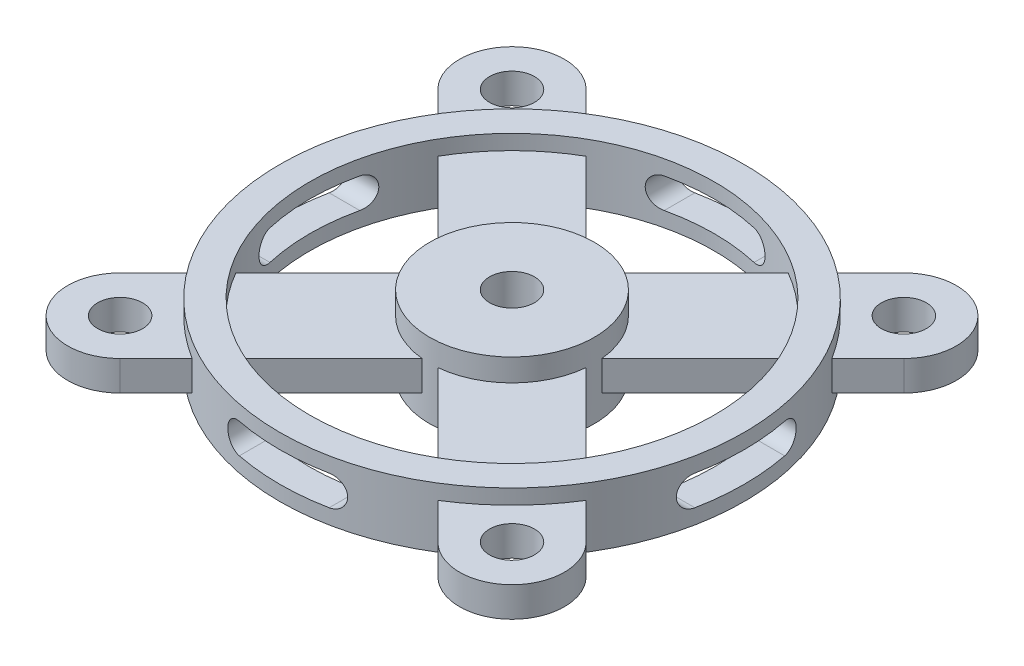
SolidWorks part; units mm, degrees
ref_plane "Front Plane" through (0, 0, 0) normal (0, 0, 1) x (1, 0, 0)
ref_plane "Top Plane" through (0, 0, 0) normal (0, 1, 0) x (1, 0, 0)
ref_plane "Right Plane" through (0, 0, 0) normal (1, 0, 0) x (0, 0, -1)
sketch "Sketch1" plane through (0, 0, 0) normal (0, 1, 0) x (1, 0, 0)
  circle A0 centre (0, 0) radius 15.5
  circle A1 centre (0, 0) radius 13.5
  dimension "D1" = 31
  dimension "D2" = 2
extrude "Boss-Extrude1" add sketch "Sketch1" along normal blind 4
sketch "Sketch2" plane through (0, 0, 0) normal (0, 0, 1) x (1, 0, 0)
  line L0 (-3, 2) -> (3, 2) construction
  line L1 (-3, 3) -> (3, 3)
  line L2 (-3, 1) -> (3, 1)
  arc A0 (-3, 3) -> (-3, 1) centre (-3, 2) ccw
  arc A1 (3, 1) -> (3, 3) centre (3, 2) ccw
  point P2 (0, 2)
  dimension "D1" = 2
  dimension "D2" = 6
  dimension "D3" = 0
  dimension "D4" = 2
extrude "Cut-Extrude1" cut sketch "Sketch2" against normal blind 44 and the other way blind 44
sketch "Sketch3" plane through (0, 0, 0) normal (1, 0, 0) x (0, 0, -1)
  line L0 (-3, 2) -> (3, 2) construction
  line L1 (-3, 3) -> (3, 3)
  line L2 (-3, 1) -> (3, 1)
  line L3 (-15.5, 0) -> (15.5, 0) construction
  arc A0 (-3, 3) -> (-3, 1) centre (-3, 2) ccw
  arc A1 (3, 1) -> (3, 3) centre (3, 2) ccw
  point P2 (0, 2)
  dimension "D1" = 6
  dimension "D2" = 2
  dimension "D3" = 0
  dimension "D4" = 2
extrude "Cut-Extrude2" cut sketch "Sketch3" against normal blind 44 and the other way blind 44
ref_plane "Plane1" through (0, 2, 0) normal (0, 1, 0) x (1, 0, 0)
sketch "Sketch4" plane through (0, 2, 0) normal (0, 1, 0) x (1, 0, 0)
  line L0 (-13.0815, 13.0815) -> (13.0815, -13.0815) construction
  line L1 (-10.6066, 15.5563) -> (15.5563, -10.6066)
  line L2 (-15.5563, 10.6066) -> (10.6066, -15.5563)
  line L3 (13.0815, 13.0815) -> (-13.0815, -13.0815) construction
  line L4 (15.5563, 10.6066) -> (-10.6066, -15.5563)
  line L5 (10.6066, 15.5563) -> (-15.5563, -10.6066)
  line L6 (0, 0) -> (0, 4.748) construction
  arc A0 (-10.6066, 15.5563) -> (-15.5563, 10.6066) centre (-13.0815, 13.0815) ccw
  arc A1 (10.6066, -15.5563) -> (15.5563, -10.6066) centre (13.0815, -13.0815) ccw
  arc A2 (15.5563, 10.6066) -> (10.6066, 15.5563) centre (13.0815, 13.0815) ccw
  arc A3 (-15.5563, -10.6066) -> (-10.6066, -15.5563) centre (-13.0815, -13.0815) ccw
  point P2 (0, 0)
  point P7 (0, 0)
  point P15 (0, 0)
  point P18 (0, 0)
  dimension "D1" = 7
  dimension "D2" = 45
  dimension "D3" = 45
  dimension "D4" = 7
  dimension "D5" = 37
  dimension "D6" = 37
extrude "Boss-Extrude2" add sketch "Sketch4" along normal blind 1 and the other way blind 1 contours L4 A2 L5 L1 | L2 A1 L1 L4 | L5 A3 L4 L2 | L1 L5 L2 L4 | L1 A0 L2 L5 region at (-8.7622, 2, -8.7622) region at (8.7622, 2, -8.7622) region at (0, 2, 0) region at (8.7622, 2, 8.7622) region at (-8.7622, 2, 8.7622)
sketch "Sketch5" plane through (0, 3, 0) normal (0, 1, 0) x (1, 0, 0)
  circle A0 centre (0, 0) radius 1.5
  dimension "D1" = 3
extrude "Cut-Extrude3" cut sketch "Sketch5" against normal blind 3
sketch "Sketch6" plane through (0, 3, 0) normal (0, 1, 0) x (1, 0, 0)
  circle A0 centre (0, 0) radius 5.5
  circle A1 centre (0, 0) radius 1.5
extrude "Boss-Extrude3" add sketch "Sketch6" along normal blind 1.5 and the other way blind 3.5
sketch "Sketch7" plane through (0, 3, 0) normal (0, 1, 0) x (1, 0, 0)
  circle A0 centre (-13.0815, 13.0815) radius 1.5
  circle A1 centre (13.0815, 13.0815) radius 1.5
  circle A2 centre (13.0815, -13.0815) radius 1.5
  circle A3 centre (-13.0815, -13.0815) radius 1.5
  point P12 (0, 0)
  dimension "D1" = 3
  dimension "D2" = 4
extrude "Cut-Extrude4" cut sketch "Sketch7" against normal blind 11.5
